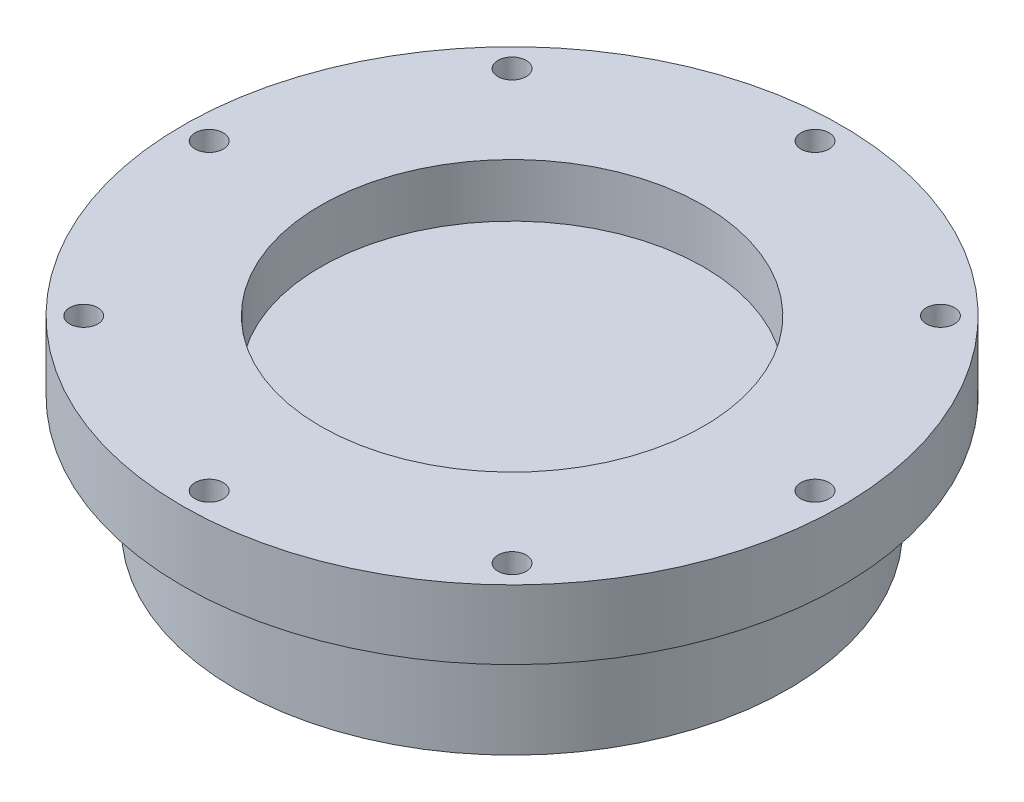
SolidWorks part; units mm, degrees
ref_plane "Front Plane" through (0, 0, 0) normal (0, 0, 1) x (1, 0, 0)
ref_plane "Top Plane" through (0, 0, 0) normal (0, 1, 0) x (1, 0, 0)
ref_plane "Right Plane" through (0, 0, 0) normal (1, 0, 0) x (0, 0, -1)
sketch "Sketch1" plane through (0, 0, 0) normal (0, 1, 0) x (1, 0, 0)
  circle A0 centre (0, 0) radius 55.88
  dimension "D1" = 111.76
extrude "Boss-Extrude1" add sketch "Sketch1" along normal blind 23.495
sketch "Sketch2" plane through (0, 23.495, 0) normal (0, 1, 0) x (1, 0, 0)
  circle A0 centre (0, 0) radius 66.675
  dimension "D1" = 133.35
extrude "Boss-Extrude2" add sketch "Sketch2" along normal blind 13.97
fillet "Fillet1" radius 7.62 1 edges at (0, 23.495, 55.88)
sketch "Sketch3" plane through (0, 37.465, 0) normal (0, 1, 0) x (1, 0, 0)
  line L0 (0, 0) -> (66.675, 0) construction
  line L1 (0, 66.675) -> (0, 0) construction
  circle A0 centre (0, 0) radius 66.675 construction
  circle A1 centre (0, 61.2775) radius 2.8575
  dimension "D1" = 5.715
  dimension "D2" = 5.3975
extrude "Cut-Extrude1" cut sketch "Sketch3" against normal through all
pattern_circular "CirPattern1" count 8 over 360 about axis through (0, 37.465, 0) along (0, 1, 0) of "Cut-Extrude1"
sketch "Sketch4" plane through (0, 37.465, 0) normal (0, 1, 0) x (1, 0, 0)
  circle A0 centre (0, 0) radius 53.975
  circle A1 centre (0, 0) radius 66.675 construction
  circle A2 centre (0, 0) radius 38.735
  dimension "D1" = 12.7
  dimension "D2" = 15.24
extrude "Cut-Extrude2" cut sketch "Sketch4" against normal blind 10.795 contours A2
